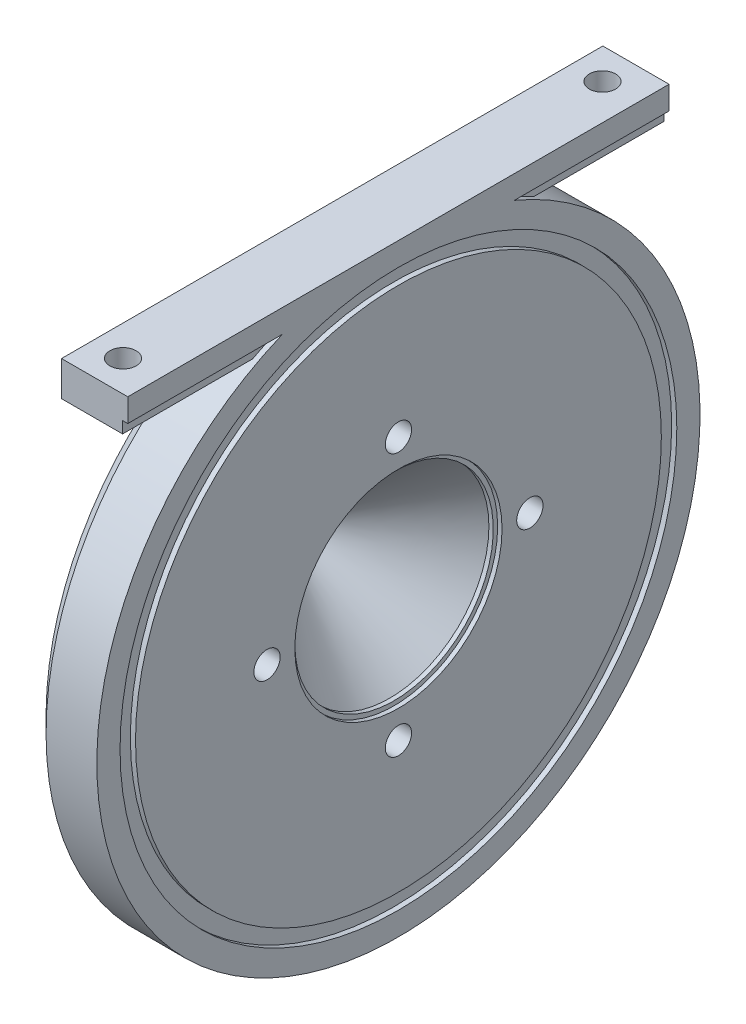
SolidWorks part; units mm, degrees
ref_plane "Front Plane" through (0, 0, 0) normal (0, 0, 1) x (1, 0, 0)
ref_plane "Top Plane" through (0, 0, 0) normal (0, 1, 0) x (1, 0, 0)
ref_plane "Right Plane" through (0, 0, 0) normal (1, 0, 0) x (0, 0, -1)
sketch "Sketch1" plane through (0, 0, 0) normal (0, 0, 1) x (1, 0, 0)
  line L0 (-801.9271, 0) -> (36107.5217, 0) construction
  line L3 (-14.0102, 3.8) -> (-14.0102, 3.15)
  line L8 (-18.3435, 1.9) -> (0, 1.9)
  line L9 (-18.3435, 1.9) -> (-18.3435, 3.15)
  line L10 (13.1623, 13.4) -> (13.1623, 39)
  line L12 (13.1623, 39) -> (4.5963, 39)
  line L16 (13.1623, 13.4) -> (12.5963, 13.4)
  line L17 (12.5963, 13.4) -> (12.5963, 12.834)
  line L18 (4.5963, 39) -> (4.5963, 12.834)
  line L20 (0, 1.9) -> (12.0303, 12.834)
  line L21 (-18.3435, 3.15) -> (-14.0102, 3.8)
  line L22 (12.0303, 12.834) -> (12.5963, 12.834)
  line L23 (-14.0102, 3.15) -> (-9.6768, 3.8)
  line L25 (-9.6768, 3.15) -> (-5.3435, 3.8)
  line L26 (-9.6768, 3.8) -> (-9.6768, 3.15)
  line L27 (-5.3435, 3.8) -> (4.5963, 12.834)
  line L28 (4.5963, 34.5) -> (13.1623, 34.5)
  line L36 (4.5963, 39) -> (13.1623, 39)
  line L38 (13.1623, 36) -> (12.4953, 36)
  line L39 (12.4953, 36) -> (12.4953, 34)
  line L40 (12.4953, 34) -> (13.1623, 34)
  dimension "D3" = 0.566
  dimension "D2" = 7.6
  dimension "D6" = 3.8
  dimension "D7" = 6.3
  dimension "D5" = 39
  dimension "D8" = 13.4
  dimension "D10" = 0.566
  dimension "D4" = 5
  dimension "D9" = 0.566
  dimension "D11" = 13
  dimension "D12" = 8.566
  dimension "D13" = 4.5
  dimension "D17" = 36
  dimension "D18" = 2
  dimension "D19" = 0.667
revolve "Revolve17" add sketch "Sketch1" angle 360 about L0 region at (5.6157, 17.6524, 0) region at (8.774, 36.79, 0)
sketch "Sketch4" plane through (4.5963, 0, 0) normal (-1, 0, 0) x (0, 0, 1)
  circle A0 centre (0, 0) radius 16.9947 construction
  point P3 (0, 16.9947)
  point P7 (16.9947, 0)
  point P12 (-16.9947, 0)
  point P13 (0, -16.9947)
hole_wizard "M3 Clearance Hole1" positions "Sketch4" profile "Sketch5" hole size "M3" standard "ISO"
sketch "Sketch5" plane through (4.5963, -16.9947, 0) normal (0, 1, 0) x (0, 0, 1)
  line L0 (0, 0) -> (0, 9.5875)
  line L1 (0, 9.5875) -> (1.7, 8.566)
  line L2 (1.7, 8.566) -> (1.7, 0)
  line L5 (1.7, 0) -> (0, 0)
  line L10 (0, 9.5875) -> (-1.7, 8.566) construction
  line L11 (0, -6.35) -> (0, 107.95) construction
  dimension "Hole Dia." = 3.4
  dimension "Hole Depth" = 8.566
  dimension "Drill Angle" = 118
chamfer "Chamfer1" distance 2 angle 45 1 edges at (4.5963, 0, 39)
extrude "Boss-Extrude1" add sketch "Sketch1<11>" against normal mid plane 70 contours L18 L28 L10 L12 region at (8.774, 36.79, 0)
sketch "Sketch1<11>" plane through (0, 0, 0) normal (0, 0, 1) x (1, 0, 0) same geometry as "Sketch1"
sketch "Sketch9" plane through (0, 34.5, 0) normal (0, -1, 0) x (-1, 0, 0)
  line L0 (-4.5963, -35) -> (-13.1623, 35) construction
  line L1 (-4.5963, -13.3697) -> (-4.5963, -35) construction
  line L2 (-4.5963, -35) -> (-12.4953, -35) construction
  line L3 (-13.1623, 35) -> (-13.1623, -18.1865) construction
  line L4 (-13.1623, 35) -> (-3.9293, 35) construction
  line L5 (-4.5963, 35) -> (-12.4953, 35) construction
  line L6 (-3.9293, 35) -> (-13.1623, -35) construction
  line L7 (-13.1623, -18.1865) -> (-13.1623, -35) construction
  line L8 (-8.5458, -35) -> (-8.5458, 35) construction
  line L9 (-4.5963, 0) -> (-13.1623, 0) construction
  line L10 (-13.1623, 39) -> (-13.1623, -39) construction
  circle A0 centre (-8.5458, -31) radius 1.7
  circle A1 centre (-8.5458, 31) radius 1.7
  dimension "D1" = 3.4
  dimension "D2" = 4
extrude "Cut-Extrude1" cut sketch "Sketch9" against normal blind 10
equation "\"D10@Sketch1\"=\"D3@Sketch1\""
equation "\"D9@Sketch1\"=\"D3@Sketch1\""
